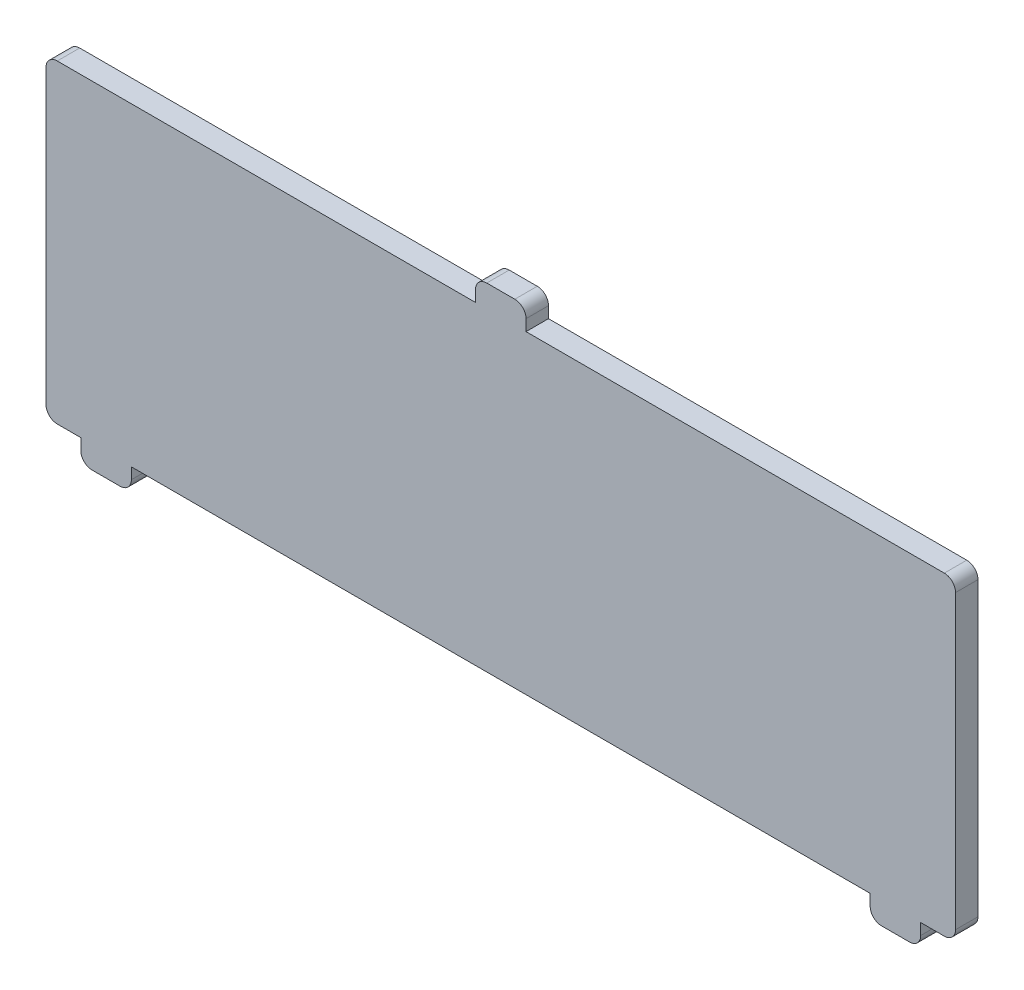
SolidWorks part; units mm, degrees
ref_plane "前基準面" through (0, 0, 0) normal (0, 0, 1) x (1, 0, 0)
ref_plane "上基準面" through (0, 0, 0) normal (0, 1, 0) x (1, 0, 0)
ref_plane "右基準面" through (0, 0, 0) normal (1, 0, 0) x (0, 0, -1)
sketch "Sketch1" plane through (0, 0, 0) normal (0, 0, 1) x (1, 0, 0)
  line L0 (0, 0) -> (0, 14) construction
  line L1 (-40.5, 14) -> (40.5, 14)
  line L2 (-40.5, 14) -> (-40.5, -14)
  line L3 (-40.5, -14) -> (40.5, -14)
  line L4 (40.5, 14) -> (40.5, -14)
  line L5 (-40.5, 14) -> (40.5, -14) construction
  line L6 (-40.5, -14) -> (40.5, 14) construction
  line L7 (0, 14) -> (0, -14) construction
  line L8 (-37.4, -14) -> (-32.9, -16) construction
  line L9 (-37.4, -14) -> (-32.9, -14)
  line L10 (-37.4, -14) -> (-37.4, -16)
  line L11 (-37.4, -16) -> (-32.9, -16)
  line L12 (-32.9, -14) -> (-32.9, -16)
  line L14 (37.4, -16) -> (32.9, -16)
  line L15 (32.9, -14) -> (32.9, -16)
  line L16 (37.4, -14) -> (32.9, -14)
  line L17 (37.4, -14) -> (37.4, -16)
  line L18 (0, 0) -> (0, 22.3502) construction
  line L19 (-2.25, 16) -> (2.25, 14) construction
  line L20 (-2.25, 14) -> (2.25, 14)
  line L21 (-2.25, 14) -> (-2.25, 16)
  line L22 (-2.25, 16) -> (2.25, 16)
  line L23 (2.25, 14) -> (2.25, 16)
  line L24 (2.25, 16) -> (-2.25, 14) construction
  line L25 (-32.9, -14) -> (-37.4, -16) construction
  point P0 (0, 0)
  point P14 (-35.15, -15)
  point P24 (0, 15)
  dimension "D1" = 81
  dimension "D2" = 28
  dimension "D3" = 2
  dimension "D4" = 4.5
  dimension "D5" = 35.15
  dimension "D6" = 2
  dimension "D7" = 4.5
extrude "Boss-Extrude1" add sketch "Sketch1" along normal mid plane 2 contours L4 L1 L2 L3 | L12 L3 L10 L11 | L17 L3 L15 L14 | L23 L22 L21 L20 region at (0, 0, 0) region at (-35.15, -15, 0) region at (35.15, -15, 0)
fillet "Fillet1" radius 1 10 edges at (-40.5, 14, 0) (-32.9, -16, 0) (-37.4, -16, 0) (-40.5, -14, 0) (32.9, -16, 0) (37.4, -16, 0) (40.5, -14, 0) (40.5, 14, 0) (2.25, 16, 0) (-2.25, 16, 0)
